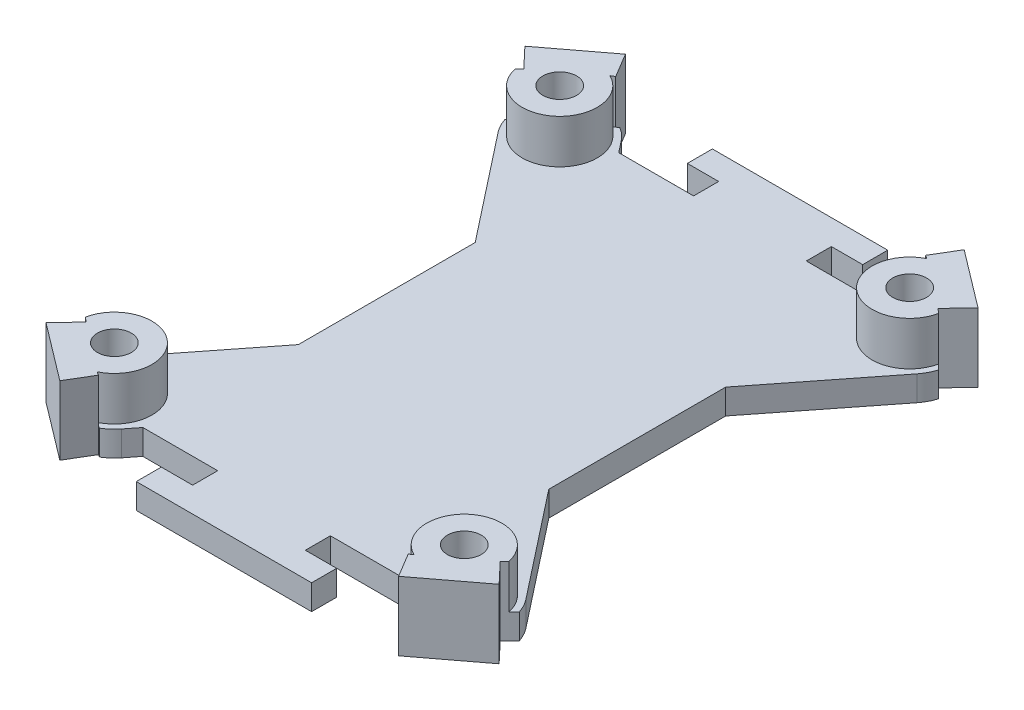
SolidWorks part; units mm, degrees
note: '?' marks a value the reader was unsure of. The reader was unsure of these and kept them because the rebuilt part matched: shared geometry of "Sketch1<3>", "Sketch1<5>".
ref_plane "Front Plane" through (0, 0, 0) normal (0, 0, 1) x (1, 0, 0)
ref_plane "Top Plane" through (0, 0, 0) normal (0, 1, 0) x (1, 0, 0)
ref_plane "Right Plane" through (0, 0, 0) normal (1, 0, 0) x (0, 0, -1)
sketch "Sketch1" plane through (0, 0, 0) normal (0, 1, 0) x (1, 0, 0)
  line L0 (0, 0) -> (0, 50000) construction
  line L1 (-13.97, 17.78) -> (13.97, 17.78) construction
  line L2 (-13.97, 17.78) -> (-13.97, -17.78) construction
  line L3 (-13.97, -17.78) -> (13.97, -17.78) construction
  line L4 (13.97, 17.78) -> (13.97, -17.78) construction
  line L5 (-13.97, 17.78) -> (13.97, -17.78) construction
  line L6 (-13.97, -17.78) -> (13.97, 17.78) construction
  line L7 (0, 0) -> (50000, 0) construction
  line L8 (0, 0) -> (18.0898, 19.1183)
  line L9 (18.0898, 19.1183) -> (13.523, 22.5805)
  line L10 (0, 0) -> (13.523, 22.5805)
  line L20 (15.8064, 20.8494) -> (16.0519, 21.1733) construction
  line L21 (-16.5, -20.62) -> (16.5, -20.62) construction
  line L22 (-16.5, -20.62) -> (-16.5, 20.62) construction
  line L23 (-16.5, 20.62) -> (16.5, 20.62) construction
  line L24 (16.5, -20.62) -> (16.5, 20.62) construction
  line L25 (-16.5, -20.62) -> (16.5, 20.62) construction
  line L26 (-16.5, 20.62) -> (16.5, -20.62) construction
  line L27 (18.0898, 19.1183) -> (18.2616, 19.2999) construction
  line L28 (0, 0) -> (13.523, -22.5805)
  line L29 (18.0898, -19.1183) -> (13.523, -22.5805)
  line L30 (0, 0) -> (18.0898, -19.1183)
  line L31 (0, 0) -> (-13.523, 22.5805)
  line L32 (-18.0898, 19.1183) -> (-13.523, 22.5805)
  line L33 (0, 0) -> (-18.0898, 19.1183)
  line L34 (0, 0) -> (-18.0898, -19.1183)
  line L35 (-18.0898, -19.1183) -> (-13.523, -22.5805)
  line L36 (0, 0) -> (-13.523, -22.5805)
  circle A0 centre (0, 0) radius 24.07
  circle A1 centre (0, 0) radius 26.5702 construction
  circle A6 centre (0, 0) radius 34.3136
  dimension "D1" = 48.14
  dimension "D8" = 53.1403
  dimension "D2" = 27.94
  dimension "D3" = 35.56
  dimension "D4" = 33
  dimension "D5" = 41.24
  dimension "D6" = 4.75
  dimension "D7" = 7.75
  dimension "D9" = 0.25
extrude "Boss-Extrude1" add sketch "Sketch1" along normal blind 2 contours L33 A0 L34 | L10 A0 L31 | L30 A0 L8 | L36 A0 L28 | L28 A0 L30 | L34 A0 L36 | L31 A0 L33 | L8 A0 L10
extrude "Boss-Extrude2" add sketch "Sketch1<3>" along normal offset from surface (5.5 mm away) 3.5 contours A0 L31 L32 L33 | A0 L8 L9 L10 | A0 L28 L29 L30 | A0 L34 L35 L36
sketch "Sketch1<3>" plane through (0, 0, 0) normal (0, 1, 0) x (1, 0, 0) same geometry as "Sketch1"
sketch "Sketch2" plane through (0, 0, 0) normal (0, 1, 0) x (1, 0, 0)
  line L4 (0, -200000) -> (0, 250000) construction
  line L5 (-200000, 0) -> (250000, 0) construction
  line L7 (0, -200000) -> (0, 250000)
  line L8 (-200000, 0) -> (250000, 0)
  circle A14 centre (13.97, 17.78) radius 3
  circle A15 centre (13.97, -17.78) radius 3
  circle A25 centre (-13.97, -17.78) radius 3
  circle A26 centre (-13.97, 17.78) radius 3
  dimension "D1" = 6
extrude "Boss-Extrude5" add sketch "Sketch2" along normal up to surface (5.5 mm away) up to face at (15.1524, 5.5, 19.9867)
ref_axis "Axis1" through (13.97, 0, -17.78) along (0, 1, 0)?
ref_axis "Axis2" through (-13.97, 0, 17.78) along (0, 1, 0)?
ref_plane "Plane1" through (0, 0, 0) normal (-0.7863, 0, -0.6178) x (-0.6178, 0, 0.7863)
sketch "Sketch3" plane through (0, 0, 0) normal (-0.7863, 0, -0.6178) x (-0.6178, 0, 0.7863)
  line L0 (19.6117, 0) -> (26.2093, 3.8091)
  line L1 (26.4079, 0) -> (6.0198, 0) construction
  line L2 (26.2093, 5.5) -> (26.2093, 0) construction
  line L3 (0, 0) -> (26.1103, 0) construction
  line L4 (19.6117, 0) -> (26.2093, 0)
  line L5 (26.2093, -3.8091) -> (26.2093, 3.8091)
  line L6 (19.6117, 5.5) -> (19.6117, 2) construction
  line L7 (0, 0) -> (0, 50000) construction
  line L8 (-26.2093, -3.8091) -> (-26.2093, 3.8091)
  line L9 (-19.6117, 0) -> (-26.2093, 0)
  line L10 (-19.6117, 0) -> (-26.2093, 3.8091)
  line L11 (-19.6117, 0) -> (-26.2093, -3.8091)
  line L12 (19.6117, 0) -> (26.2093, -3.8091)
  dimension "D1" = 30
extrude "Boss-Extrude6" [suppressed] add sketch "Sketch3" along normal up to vertex and the other way up to vertex contours L4 L12 L5 | L11 L9 L8
mirror "Mirror1" [suppressed] about plane through (0, 0, 0) normal (1, 0, 0)
extrude "Cut-Extrude3" cut sketch "Sketch1<5>" along normal through all both and the other way through all contours A6 A0 L30 L29 L28 L36 L35 L34 L33 L32 L31 L10 L9 L8
sketch "Sketch1<5>" plane through (0, 0, 0) normal (0, 1, 0) x (1, 0, 0) same geometry as "Sketch1"
hole_wizard "M2.5 Clearance Hole1" positions "Sketch6" profile "Sketch7" hole size "M2.5" standard "ANSI Metric" end condition through all
sketch "Sketch6" plane through (0, 5.5, 0) normal (0, 1, 0) x (1, 0, 0)
  point P0 (-13.97, 17.78)
  point P3 (13.97, 17.78)
  point P6 (13.97, -17.78)
  point P9 (-13.97, -17.78)
sketch "Sketch7" plane through (-13.97, 5.5, -17.78) normal (1, 0, 0) x (0, 0, 1)
  line L0 (0, 0) -> (0, 5.5005)
  line L1 (0, 5.5005) -> (1.35, 5.5005)
  line L2 (1.35, 5.5005) -> (1.35, 0)
  line L5 (1.35, 0) -> (0, 0)
  line L11 (0, -6.35) -> (0, 107.95) construction
  dimension "Thru Hole Dia." = 2.7
  dimension "Thru Hole Depth" = 5.5005
sketch "Sketch8" plane through (0, 0, 0) normal (0, -1, 0) x (1, 0, 0)
  line L0 (-13.97, 17.78) -> (13.97, -17.78) construction
  line L1 (-11.2179, 19.9424) -> (16.7221, -15.6176)
  line L2 (-16.7221, 15.6176) -> (11.2179, -19.9424)
  line L3 (13.97, 17.78) -> (-13.97, -17.78) construction
  line L4 (16.7221, 15.6176) -> (-11.2179, -19.9424)
  line L5 (11.2179, 19.9424) -> (-16.7221, -15.6176)
  line L6 (-7, -23) -> (-7, -21)
  line L7 (-7, -23) -> (7, -23)
  line L8 (0, 0) -> (0, 50000) construction
  line L9 (0, 0) -> (50000, 0) construction
  line L10 (-7, -21) -> (-4.5, -21)
  line L11 (-4.5, -21) -> (-4.5, -19)
  line L12 (-4.5, -19) -> (-10.4774, -19)
  line L13 (4.5, -19) -> (10.4774, -19)
  line L14 (4.5, -21) -> (4.5, -19)
  line L15 (7, -21) -> (4.5, -21)
  line L16 (7, -23) -> (7, -21)
  line L17 (7, 23) -> (7, 21)
  line L18 (7, 21) -> (4.5, 21)
  line L19 (4.5, 21) -> (4.5, 19)
  line L20 (4.5, 19) -> (10.4774, 19)
  line L21 (-4.5, 19) -> (-10.4774, 19)
  line L22 (-4.5, 21) -> (-4.5, 19)
  line L23 (-7, 21) -> (-4.5, 21)
  line L24 (-7, 23) -> (7, 23)
  line L25 (-7, 23) -> (-7, 21)
  line L26 (-10, -7.0622) -> (-10, 7.0622)
  line L27 (10, -7.0622) -> (10, 7.0622)
  arc A0 (-11.2179, 19.9424) -> (-16.7221, 15.6176) centre (-13.97, 17.78) ccw
  arc A1 (11.2179, -19.9424) -> (16.7221, -15.6176) centre (13.97, -17.78) ccw
  arc A2 (16.7221, 15.6176) -> (11.2179, 19.9424) centre (13.97, 17.78) ccw
  arc A3 (-16.7221, -15.6176) -> (-11.2179, -19.9424) centre (-13.97, -17.78) ccw
  circle A4 centre (0, 0) radius 34.9219
  point P4 (0, 0)
  point P9 (0, 0)
  point P27 (0, 23)
  point P32 (0, -23)
  point P39 (0, -23)
  point P50 (-10, 0)
  arc M14 (16.5433, -17.4839) -> (16.5433, 17.4839) centre (0, 0) ccw
  arc M18 (12.3669, 20.65) -> (-12.3669, 20.65) centre (0, 0) ccw
  arc M22 (-16.5433, 17.4839) -> (-16.5433, -17.4839) centre (0, 0) ccw
  arc M26 (-12.3669, -20.65) -> (12.3669, -20.65) centre (0, 0) ccw
  dimension "D1" = 7
  dimension "D2" = 7
  dimension "D3" = 23
  dimension "D4" = 2
  dimension "D5" = 2
  dimension "D6" = 2.5
  dimension "D7" = 10
extrude "Cut-Extrude4" cut sketch "Sketch8" against normal through all contours A4 A3 A0 A2 A1 M22 M18 M14 M26 | A3 L5 L2 A0 M22 | A2 A0 L1 L5 M18 | A2 L4 L1 A1 M14 | A3 A1 L2 L4 M26
ref_plane "Plane2" [suppressed] through (0, 2, 0) normal (0, 1, 0) x (1, 0, 0)
other "SurfaceCut1" [suppressed]
sketch "Sketch9" plane through (0, 0, 0) normal (0, 1, 0) x (1, 0, 0)
  line L44 (11.5427, -15.5) -> (3.5, -5.2638)
  line L45 (3.5, -5.2638) -> (3.5, -15.5)
  line L46 (3.5, -15.5) -> (11.5427, -15.5)
  line L47 (10.4774, -19) -> (4.5, -19) construction
  line L48 (10, -7.0622) -> (16.7221, -15.6176) construction
  line L49 (0, 0) -> (0, 50000) construction
  line L50 (0, 0) -> (50000, 0) construction
  line L51 (-3.5, -15.5) -> (-11.5427, -15.5)
  line L52 (-3.5, -5.2638) -> (-3.5, -15.5)
  line L53 (-11.5427, -15.5) -> (-3.5, -5.2638)
  line L54 (3.5, 15.5) -> (11.5427, 15.5)
  line L55 (3.5, 5.2638) -> (3.5, 15.5)
  line L56 (11.5427, 15.5) -> (3.5, 5.2638)
  line L57 (-11.5427, 15.5) -> (-3.5, 5.2638)
  line L58 (-3.5, 5.2638) -> (-3.5, 15.5)
  line L59 (-3.5, 15.5) -> (-11.5427, 15.5)
  dimension "D1" = 3.5
  dimension "D2" = 4
  dimension "D3" = 3.5
extrude "Cut-Extrude5" [suppressed] cut sketch "Sketch9" against normal through all both and the other way through all
fillet "Fillet1" [suppressed] radius 0.5
equation "\"D1@Sketch1\"=24.57*2-1"
